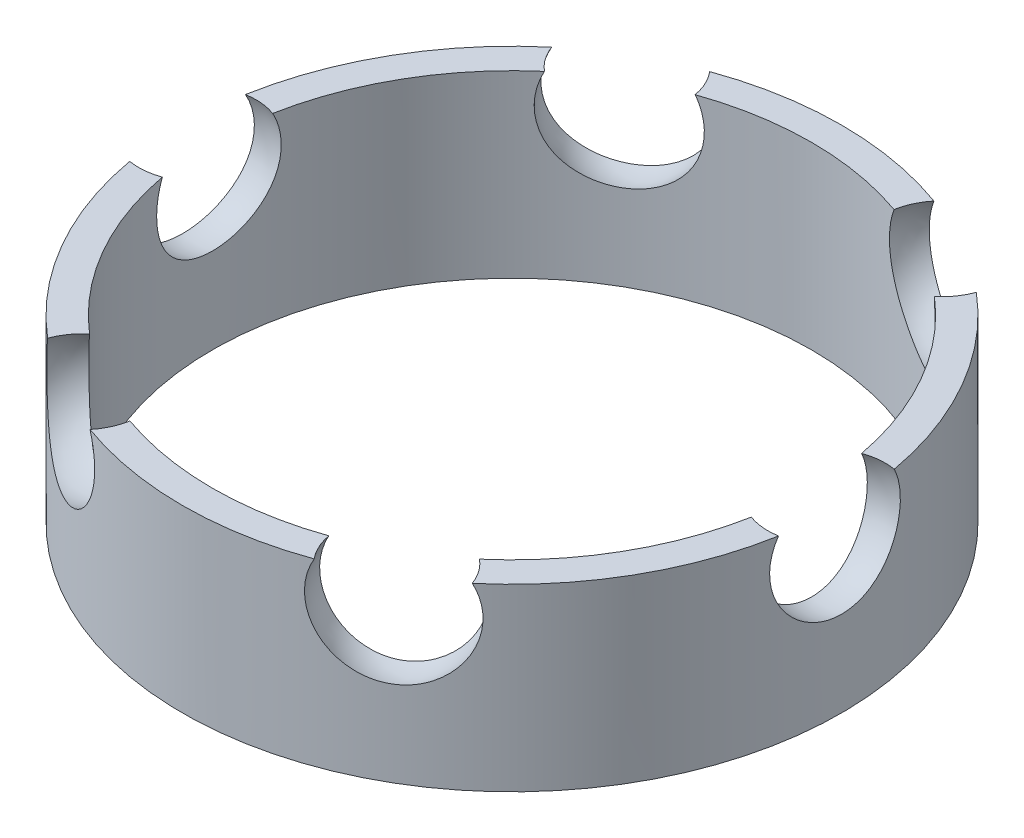
SolidWorks part; units mm, degrees
ref_plane "Front Plane" through (0, 0, 0) normal (0, 0, 1) x (1, 0, 0)
ref_plane "Top Plane" through (0, 0, 0) normal (0, 1, 0) x (1, 0, 0)
ref_plane "Right Plane" through (0, 0, 0) normal (1, 0, 0) x (0, 0, -1)
sketch "Sketch2" plane through (0, 0, 0) normal (0, 0, 1) x (1, 0, 0)
  line L0 (0, 0) -> (0, 19.8196) construction
  line L1 (0, 0) -> (10.5, 0) construction
  line L2 (8.9444, 1.5556) -> (9.5, 2.1113)
  line L3 (10.5, 0) -> (10.5, 10.5941) construction
  line L4 (9.5, 2.1113) -> (9.5, 5.5)
  line L5 (9.5, 5.5) -> (5, 5.5)
  line L6 (5, 5.5) -> (5, -5.5)
  line L7 (12.0556, 1.5556) -> (11.5, 2.1113)
  line L8 (11.5, 2.1113) -> (11.5, 5.5)
  line L9 (11.5, 5.5) -> (16, 5.5)
  line L10 (16, 5.5) -> (16, -5.5)
  line L11 (12.0556, -1.5556) -> (11.5, -2.1113)
  line L12 (8.9444, -1.5556) -> (9.5, -2.1113)
  line L13 (11.5, -5.5) -> (16, -5.5)
  line L14 (11.5, -2.1113) -> (11.5, -5.5)
  line L15 (9.5, -2.1113) -> (9.5, -5.5)
  line L16 (9.5, -5.5) -> (5, -5.5)
  line L17 (16, 0) -> (18.4, 0) construction
  line L18 (18.4, -3.1) -> (18.4, 3.1)
  line L19 (18.4, 3.1) -> (16, 5.5)
  line L20 (18.4, -3.1) -> (16, -5.5)
  line L26 (5, 5.5) -> (2.5, 5.5)
  line L27 (5, 5.5) -> (5, -5.5)
  line L28 (5, -5.5) -> (2.5, -5.5)
  line L29 (2.5, 5.5) -> (2.5, -5.5)
  arc A0 (8.9444, -1.5556) -> (8.9444, 1.5556) centre (10.5, 0) cw
  circle A1 centre (10.5, 0) radius 2 construction
  arc A2 (12.0556, -1.5556) -> (12.0556, 1.5556) centre (10.5, 0) ccw
  point P22 (16, 0)
  point P25 (5, 0)
  point P30 (18.4, 0)
  dimension "D1" = 45
  dimension "D2" = 2.2
  dimension "D3" = 4
  dimension "D4" = 2
  dimension "D5" = 6.2
  dimension "D6" = 45
  dimension "D7" = 11
  dimension "D8" = 5
  dimension "D9" = 10.5
  dimension "D10" = 2.5
sketch "Sketch3" plane through (0, 0, 0) normal (0, 0, 1) x (1, 0, 0)
  line L1 (10, -5) -> (11, -5)
  line L2 (10, -5) -> (10, 5)
  line L3 (10, 5) -> (11, 5)
  line L4 (11, -5) -> (11, 5)
  line L5 (10, -5) -> (11, 5) construction
  line L6 (10, 5) -> (11, -5) construction
  line L7 (0, 0) -> (0, 7.9473) construction
  line L8 (0, 0) -> (0, 19.8196) construction
  point P0 (10.5, 0)
  dimension "D1" = 1
  dimension "D2" = 10
sketch "Sketch4" plane through (0, 0, 0) normal (0, 0, 1) x (1, 0, 0)
  line L0 (10, -5) -> (11, 5) construction
  line L3 (10.5, -2.2) -> (10.5, 2.2)
  circle A1 centre (10.5, 0) radius 2.2
  point P4 (10.5, 0)
  point P9 (10.5, 0)
revolve "Revolve3" add sketch "Sketch3" angle 360 about L7
revolve "Cut-Revolve1" cut sketch "Sketch4" angle 360 about L3 region at (11.4337, 0, 0)
pattern_circular "CirPattern1" count 6 over 360 about axis through (0, 5, 0) along (0, -1, 0) of "Cut-Revolve1"
sketch "Sketch5" plane through (0, 5, 0) normal (0, 1, 0) x (1, 0, 0)
  circle A0 centre (0, 0) radius 10
  circle A1 centre (0, 0) radius 11
extrude "Cut-Extrude1" cut sketch "Sketch5" against normal blind 4
